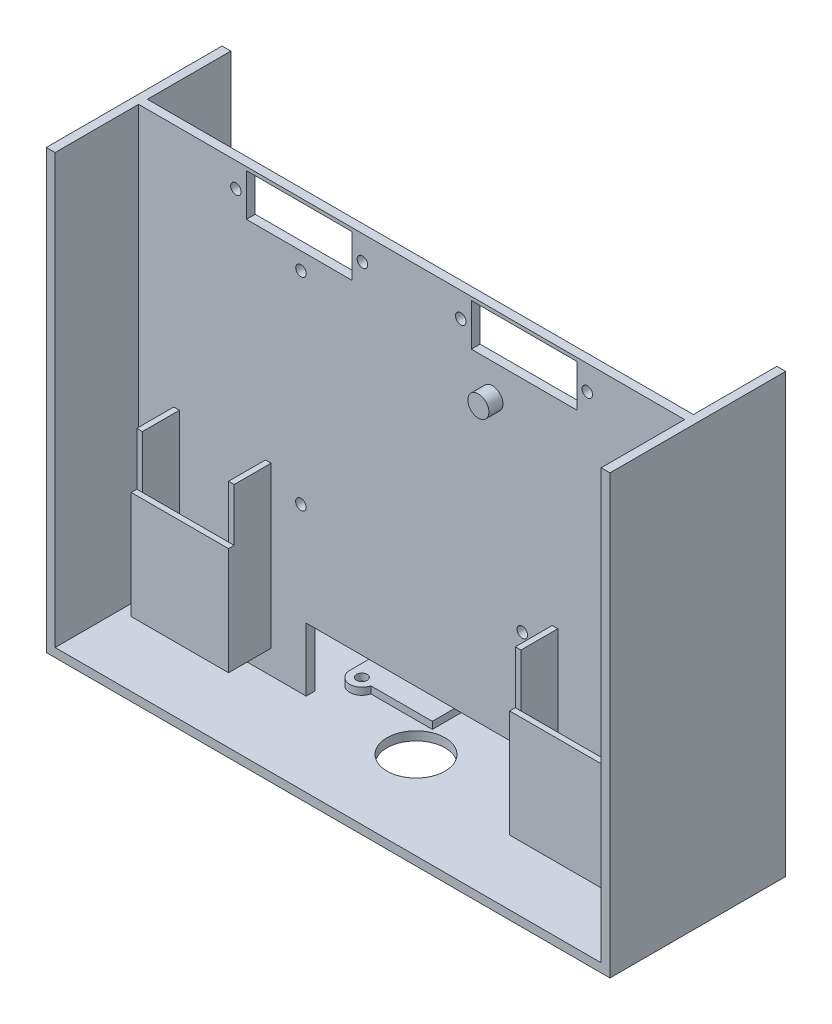
SolidWorks part; units mm, degrees
ref_plane "Front Plane" through (0, 0, 0) normal (0, 0, 1) x (1, 0, 0)
ref_plane "Top Plane" through (0, 0, 0) normal (0, 1, 0) x (1, 0, 0)
ref_plane "Right Plane" through (0, 0, 0) normal (1, 0, 0) x (0, 0, -1)
sketch "Sketch1" plane through (0, 0, 0) normal (0, 0, 1) x (1, 0, 0)
  line L1 (0, 0) -> (155.4, 0)
  line L2 (0, 0) -> (0, 122)
  line L3 (0, 122) -> (155.4, 122)
  line L4 (155.4, 0) -> (155.4, 122)
  line L5 (42.7, 43) -> (112.7, 43) construction
  line L6 (42.7, 43) -> (42.7, 108) construction
  line L7 (42.7, 108) -> (112.7, 108) construction
  line L8 (112.7, 43) -> (112.7, 108) construction
  line L9 (30.7, 121) -> (60.7, 121)
  line L10 (30.7, 121) -> (30.7, 109)
  line L11 (30.7, 109) -> (60.7, 109)
  line L12 (60.7, 121) -> (60.7, 109)
  line L13 (94.7, 109) -> (124.7, 109)
  line L14 (94.7, 109) -> (94.7, 121)
  line L15 (94.7, 121) -> (124.7, 121)
  line L16 (124.7, 109) -> (124.7, 121)
  line L35 (145.4, 52.4) -> (145.4, 6.8)
  line L36 (145.4, 6.8) -> (117.7, 6.8)
  line L37 (117.7, 6.8) -> (117.7, 52.4)
  line L38 (77.7, 122) -> (77.7, 0) construction
  line L40 (119.3, 52.4) -> (119.3, 8.4)
  line L41 (119.3, 8.4) -> (143.8, 8.4)
  line L42 (143.8, 52.4) -> (143.8, 8.4)
  line L43 (10, 6.8) -> (37.7, 6.8)
  line L44 (10, 52.4) -> (10, 6.8)
  line L46 (37.7, 6.8) -> (37.7, 52.4)
  line L47 (36.1, 52.4) -> (36.1, 8.4)
  line L48 (36.1, 8.4) -> (11.6, 8.4)
  line L49 (11.6, 52.4) -> (11.6, 8.4)
  line L51 (10, 52.4) -> (11.6, 52.4)
  line L52 (36.1, 52.4) -> (37.7, 52.4)
  line L53 (119.3, 52.4) -> (117.7, 52.4)
  line L54 (143.8, 52.4) -> (145.4, 52.4)
  circle A0 centre (46.223, 104.1) radius 1.5
  circle A1 centre (46.2, 46.5) radius 1.5
  circle A2 centre (109.2, 46.5) radius 1.5
  circle A3 centre (63.7, 115) radius 1.5
  circle A4 centre (27.7, 115) radius 1.5
  circle A5 centre (91.7, 115) radius 1.5
  circle A6 centre (127.7, 115) radius 1.5
  circle A7 centre (100.7, 100) radius 3
  dimension "D16" = 3
  dimension "D17" = 3.523
  dimension "D18" = 3.9
  dimension "D19" = 3
  dimension "D20" = 3
  dimension "D25" = 3
  dimension "D28" = 3
  dimension "D31" = 3
  dimension "D32" = 3
  dimension "D37" = 6
  dimension "D1" = 155.4
  dimension "D2" = 122
  dimension "D3" = 42.7
  dimension "D4" = 14
  dimension "D5" = 65
  dimension "D6" = 70
  dimension "D7" = 12
  dimension "D8" = 1
  dimension "D9" = 30
  dimension "D10" = 12
  dimension "D11" = 30
  dimension "D12" = 12
  dimension "D13" = 1
  dimension "D14" = 12
  dimension "D15" = 70
  dimension "D21" = 3.5
  dimension "D22" = 3.5
  dimension "D23" = 3.5
  dimension "D24" = 3.5
  dimension "D26" = 6
  dimension "D27" = 3
  dimension "D29" = 3
  dimension "D30" = 6
  dimension "D33" = 6
  dimension "D34" = 6
  dimension "D35" = 3
  dimension "D36" = 3
  dimension "D38" = 12
  dimension "D39" = 8
  dimension "D40" = 27.7
  dimension "D41" = 1.6
  dimension "D43" = 5
  dimension "D44" = 24.5
  dimension "D45" = 44
  dimension "D47" = 1.6
extrude "Boss-Extrude1" add sketch "Sketch1" along normal blind 2.5 contours L1 L4 L3 L2 A7 A6 A5 A4 A3 A2 A1 A0 L16 L13 L14 L15 L9 L12 L11 L10 | A7 | L47 L49 L48 | L43 L46 L44 L47 L48 L49 | L42 L40 L41 | L37 L36 L35 L42 L41 L40 region at (77.676, 59.4116, 0) region at (144.8665, 29.6, 0) region at (10.5335, 29.6, 0) region at (100.7, 100, 0)
extrude "Boss-Extrude2" add sketch "Sketch1<5>" along normal blind 6.5 contours A7
sketch "Sketch1<5>" plane through (0, 0, 0) normal (0, 0, 1) x (1, 0, 0) same geometry as "Sketch1"
extrude "Boss-Extrude3" add sketch "Sketch1<6>" along normal blind 13 contours L43 L46 L44 L47 L48 L49 | L37 L36 L35 L42 L41 L40 region at (144.8665, 29.6, 0) region at (10.5335, 29.6, 0)
sketch "Sketch1<6>" plane through (0, 0, 0) normal (0, 0, 1) x (1, 0, 0) same geometry as "Sketch1"
sketch "Sketch2" plane through (0, 0, 13) normal (0, 0, 1) x (1, 0, 0)
  line L0 (10, 52.4) -> (10, 6.8) construction
  line L1 (10, 37.4) -> (37.7, 37.4)
  line L2 (10, 37.4) -> (10, 6.8)
  line L3 (10, 6.8) -> (37.7, 6.8)
  line L4 (37.7, 37.4) -> (37.7, 6.8)
  line L6 (117.7, 6.8) -> (117.7, 52.4) construction
  line L7 (117.7, 37.4) -> (145.4, 37.4)
  line L8 (117.7, 37.4) -> (117.7, 6.8)
  line L9 (117.7, 6.8) -> (145.4, 6.8)
  line L10 (145.4, 37.4) -> (145.4, 6.8)
  line L12 (10, 52.4) -> (11.6, 52.4) construction
  line L13 (119.3, 52.4) -> (117.7, 52.4) construction
  dimension "D1" = 15
  dimension "D2" = 15
extrude "Boss-Extrude4" add sketch "Sketch2" along normal blind 1.6
sketch "Sketch3" plane through (0, 0, 0) normal (0, -1, 0) x (1, 0, 0)
  line L0 (0, 2.5) -> (155.4, 2.5) construction
  line L1 (0, -23.75) -> (155.4, -23.75)
  line L2 (0, -23.75) -> (0, 26.25)
  line L3 (0, 26.25) -> (155.4, 26.25)
  line L4 (155.4, -23.75) -> (155.4, 26.25)
  line L6 (0, -23.75) -> (155.4, 26.25) construction
  line L7 (155.4, -23.75) -> (0, 26.25) construction
  circle A0 centre (77.7, 1.25) radius 8.25
  dimension "D3" = 16.5
  dimension "D1" = 50
  dimension "D2" = 23.75
extrude "Boss-Extrude5" add sketch "Sketch3" along normal blind 2.5
sketch "Sketch4" plane through (0, 0, 2.5) normal (0, 0, 1) x (1, 0, 0)
  line L0 (0, 0) -> (69.5452, 0) construction
  line L1 (47.7, 0) -> (107.7, 0)
  line L2 (47.7, 0) -> (47.7, 18)
  line L3 (47.7, 18) -> (107.7, 18)
  line L4 (107.7, 0) -> (107.7, 18)
  line L5 (0, 0) -> (0, 122) construction
  dimension "D1" = 18
  dimension "D2" = 47.7
  dimension "D3" = 60
extrude "Cut-Extrude1" cut sketch "Sketch4" against normal blind 10
sketch "Sketch6" plane through (0, 18, 0) normal (0, -1, 0) x (1, 0, 0)
  line L0 (89.85, 8.759) -> (72.3538, 8.759)
  line L1 (66.55, -7.65) -> (88.85, -7.65) construction
  line L2 (66.55, -7.65) -> (66.55, 12.55) construction
  line L3 (66.55, 12.55) -> (88.85, 12.55) construction
  line L4 (88.85, -7.65) -> (88.85, 12.55) construction
  line L5 (107.7, 0) -> (47.7, 0) construction
  line L6 (65.55, -8.65) -> (89.85, -8.65)
  line L7 (65.55, -8.65) -> (65.55, 7.95)
  line L9 (89.85, -8.65) -> (89.85, 8.759)
  circle A0 centre (69, 7.95) radius 1.5
  circle A1 centre (86.4, -5.45) radius 1.5
  circle A2 centre (77.7, 1.25) radius 8.25 construction
  arc A3 (72.3538, 8.759) -> (65.55, 7.95) centre (69, 7.95) ccw
  dimension "D9" = 3
  dimension "D13" = 3
  dimension "D1" = 20.2
  dimension "D2" = 22.3
  dimension "D3" = 1
  dimension "D4" = 1
  dimension "D6" = 24.3
  dimension "D7" = 7.65
  dimension "D8" = 4.6
  dimension "D10" = 2.45
  dimension "D11" = 2.2
  dimension "D12" = 2.45
  dimension "D14" = 11.15
extrude "Boss-Extrude6" add sketch "Sketch6" along normal blind 2
sketch "Sketch7" plane through (155.4, 0, 0) normal (1, 0, 0) x (0, 0, -1)
  line L1 (23.75, -2.5) -> (-26.25, -2.5)
  line L2 (23.75, -2.5) -> (23.75, 122)
  line L3 (23.75, 122) -> (-26.25, 122)
  line L4 (-26.25, -2.5) -> (-26.25, 122)
  dimension "D1" = 50
  dimension "D2" = 124.5
extrude "Boss-Extrude7" add sketch "Sketch7" along normal blind 2.5
sketch "Sketch8" plane through (0, 0, 0) normal (-1, 0, 0) x (0, 0, 1)
  line L1 (-23.75, 122) -> (26.25, 122)
  line L2 (-23.75, 122) -> (-23.75, -2.5)
  line L3 (-23.75, -2.5) -> (26.25, -2.5)
  line L4 (26.25, 122) -> (26.25, -2.5)
extrude "Boss-Extrude8" add sketch "Sketch8" along normal blind 2.5
